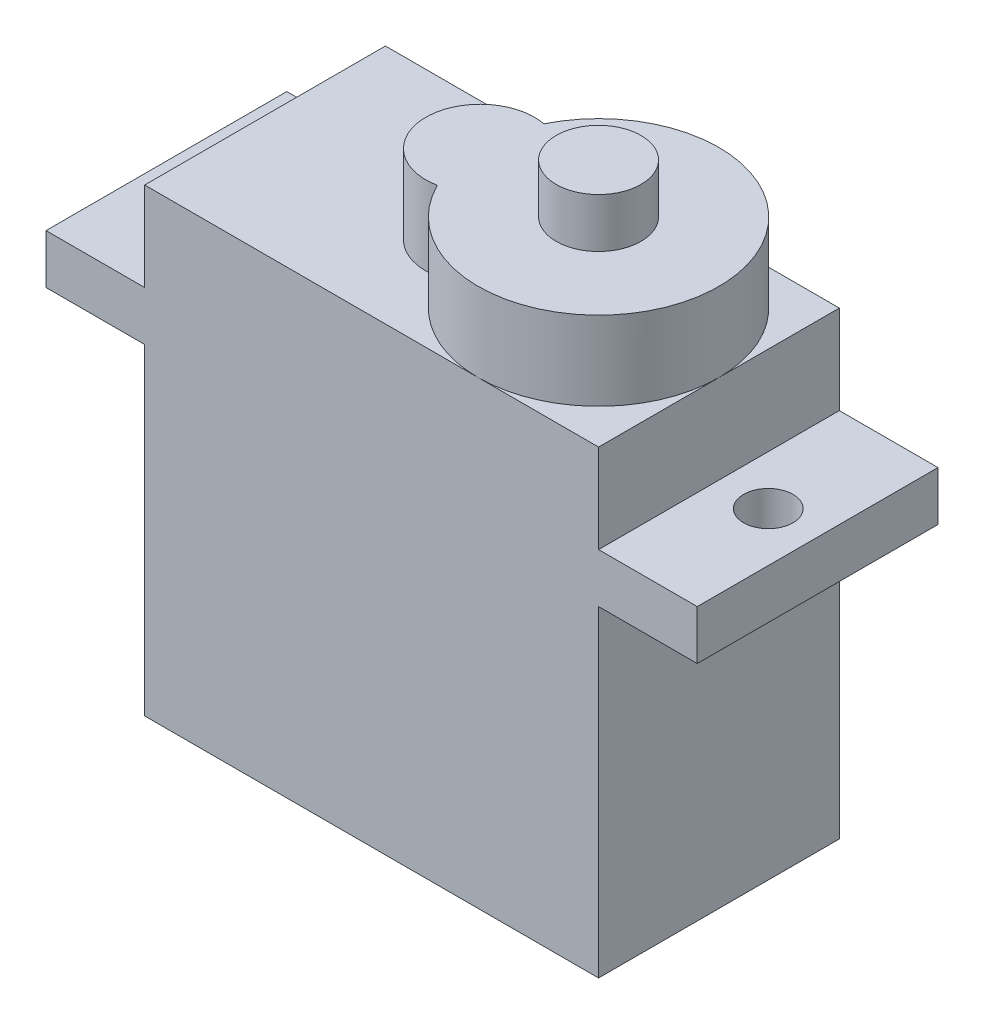
SolidWorks part; units mm, degrees
ref_plane "Front Plane" through (0, 0, 0) normal (0, 0, 1) x (1, 0, 0)
ref_plane "Top Plane" through (0, 0, 0) normal (0, 1, 0) x (1, 0, 0)
ref_plane "Right Plane" through (0, 0, 0) normal (1, 0, 0) x (0, 0, -1)
sketch "Sketch1" plane through (0, 0, 0) normal (0, 1, 0) x (1, 0, 0)
  line L1 (11.5, 6.1) -> (-11.5, 6.1)
  line L2 (11.5, 6.1) -> (11.5, -6.1)
  line L3 (11.5, -6.1) -> (-11.5, -6.1)
  line L4 (-11.5, 6.1) -> (-11.5, -6.1)
  line L5 (11.5, 6.1) -> (-11.5, -6.1) construction
  line L6 (11.5, -6.1) -> (-11.5, 6.1) construction
  point P0 (0, 0)
  dimension "D1" = 23
  dimension "D2" = 12.2
extrude "Boss-Extrude1" add sketch "Sketch1" along normal blind 23.3
sketch "Sketch2" plane through (0, 23.3, 0) normal (0, 1, 0) x (1, 0, 0)
  line L0 (-11.5, 6.1) -> (-16.5, 6.1)
  line L1 (-16.5, 6.1) -> (-16.5, -6.1)
  line L2 (-16.5, -6.1) -> (-11.5, -6.1)
  line L3 (-11.5, -6.1) -> (-11.5, 6.1)
  line L4 (0, 7.0655) -> (0, -7.0893) construction
  line L5 (16.5, -6.1) -> (11.5, -6.1)
  line L6 (16.5, 6.1) -> (16.5, -6.1)
  line L7 (11.5, 6.1) -> (16.5, 6.1)
  line L8 (11.5, -6.1) -> (11.5, 6.1)
  circle A0 centre (-14, 0) radius 1.25
  circle A1 centre (14, 0) radius 1.25
  point P15 (0, 0)
  dimension "D2" = 2.5
  dimension "D1" = 5
  dimension "D3" = 28
extrude "Boss-Extrude2" add sketch "Sketch2" against normal blind 2.5 from offset 4.5 offset against normal yes
sketch "Sketch3" plane through (0, 23.3, 0) normal (0, 1, 0) x (1, 0, 0)
  line L0 (11.5, 6.1) -> (11.5, -6.1) construction
  line L1 (11.5, 6.1) -> (-11.5, 6.1) construction
  line L2 (-11.5, -6.1) -> (11.5, -6.1) construction
  arc A0 (-0.0706, -2.6986) -> (-0.0706, 2.6986) centre (5.4, 0) ccw
  arc A1 (-0.0706, 2.6986) -> (-0.0706, -2.6986) centre (-0.6, 0) ccw
  circle A2 centre (5.4, 0) radius 2.15
  dimension "D2" = 5.5
  dimension "D3" = 4.3
  dimension "D1" = 6
extrude "Boss-Extrude3" add sketch "Sketch3" along normal blind 4 contours A2 | A0 A1 A2 region at (-3.1578, 23.3, 0) region at (5.4, 23.3, 0)
extrude "Boss-Extrude4" add sketch "Sketch3<4>" along normal blind 2.5 from surface contours A2 region at (5.4, 23.3, 0) starting at face at (4.075, 27.3, 0)
sketch "Sketch3<4>" plane through (0, 23.3, 0) normal (0, 1, 0) x (1, 0, 0) same geometry as "Sketch3"
